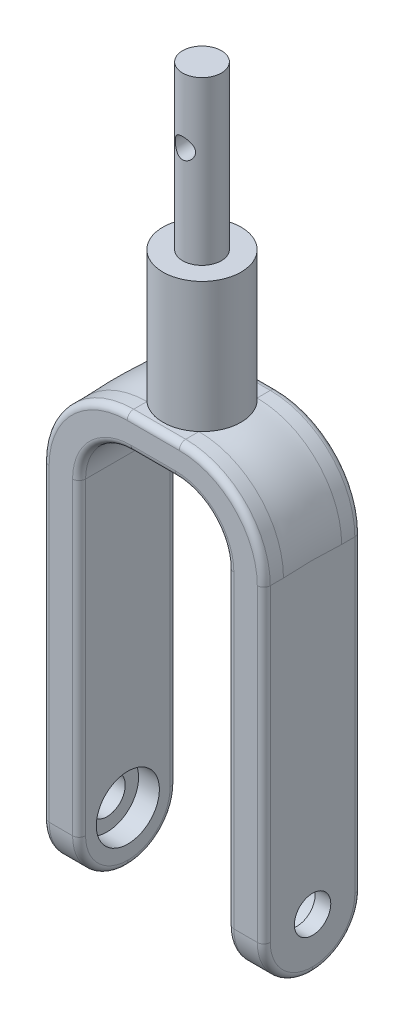
SolidWorks part; units mm, degrees
ref_plane "前视基准面" through (0, 0, 0) normal (0, 0, 1) x (1, 0, 0)
ref_plane "上视基准面" through (0, 0, 0) normal (0, 1, 0) x (1, 0, 0)
ref_plane "右视基准面" through (0, 0, 0) normal (1, 0, 0) x (0, 0, -1)
sketch "草图1" plane through (0, 0, 0) normal (0, 1, 0) x (1, 0, 0)
  line L1 (17, 7.5) -> (-17, 7.5)
  line L2 (17, 7.5) -> (17, -7.5)
  line L3 (17, -7.5) -> (-17, -7.5)
  line L4 (-17, 7.5) -> (-17, -7.5)
  line L5 (17, 7.5) -> (-17, -7.5) construction
  line L6 (17, -7.5) -> (-17, 7.5) construction
  point P0 (0, 0)
extrude "凸台-拉伸1" add sketch "草图1" against normal blind 68
sketch "草图2" plane through (0, 0, 0) normal (0, 1, 0) x (1, 0, 0)
  circle A0 centre (0, 0) radius 6
extrude "凸台-拉伸2" add sketch "草图2" along normal blind 20
sketch "草图7" plane through (0, 20, 0) normal (0, 1, 0) x (1, 0, 0)
  circle A0 centre (0, 0) radius 2.98
extrude "凸台-拉伸3" add sketch "草图7" along normal blind 25
sketch "草图8" plane through (0, 0, 0) normal (0, 0, 1) x (1, 0, 0)
  line L0 (0, 20) -> (0, 35) construction
  line L1 (6, 20) -> (-6, 20) construction
  circle A1 centre (0, 35) radius 1.55
extrude "切除-拉伸5" cut sketch "草图8" against normal through all both and the other way through all
sketch "草图3" plane through (0, 0, 7.5) normal (0, 0, 1) x (1, 0, 0)
  line L0 (-17, -68) -> (17, -68) construction
  line L1 (-11.4, -68) -> (11.4, -68)
  line L2 (-11.4, -68) -> (-11.4, -5)
  line L3 (-11.4, -5) -> (11.4, -5)
  line L4 (11.4, -68) -> (11.4, -5)
  point P6 (0, 0)
  point P7 (0, 0)
extrude "切除-拉伸1" cut sketch "草图3" against normal through all
fillet "圆角1" radius 8 2 edges at (11.4, -5, 0) (-11.4, -5, 0)
fillet "圆角5" radius 13 2 edges at (17, 0, 0) (-17, 0, 0)
fillet "圆角3" radius 7.5 4 edges at (14.2, -68, -7.5) (14.2, -68, 7.5) (-14.2, -68, -7.5) (-14.2, -68, 7.5)
fillet "圆角2" radius 1 28 edges at (-17, -36.75, -7.5) (0, 0, -7.5) (17, -36.75, -7.5) (17, -36.75, 7.5) (0, 0, 7.5) (-17, -36.75, 7.5) (-9.0569, -7.3431, 7.5) (0, -5, 7.5) (9.0569, -7.3431, 7.5) (11.4, -36.75, 7.5) (11.4, -36.75, -7.5) (9.0569, -7.3431, -7.5) (0, -5, -7.5) (-9.0569, -7.3431, -7.5) (-11.4, -36.75, -7.5) (-11.4, -36.75, 7.5) (11.4, -65.8033, 5.3033) (11.4, -65.8033, -5.3033) (-11.4, -65.8033, -5.3033) (-11.4, -65.8033, 5.3033) (-17, -65.8033, 5.3033) (-17, -65.8033, -5.3033) (17, -65.8033, -5.3033) (17, -65.8033, 5.3033) (-13.1924, -3.8076, -7.5) (13.1924, -3.8076, -7.5) (13.1924, -3.8076, 7.5) (-13.1924, -3.8076, 7.5)
sketch "草图4" plane through (17, 0, 0) normal (1, 0, 0) x (0, 0, -1)
  circle A0 centre (0, -60) radius 2.8
extrude "切除-拉伸2" cut sketch "草图4" against normal through all
sketch "草图6" plane through (11.4, 0, 0) normal (1, 0, 0) x (0, 0, -1)
  circle A0 centre (0, -60) radius 4.85
extrude "切除-拉伸4" cut sketch "草图6" along normal blind 3.2
mirror "镜向1" about plane through (0, 0, 0) normal (1, 0, 0) of "切除-拉伸4"
